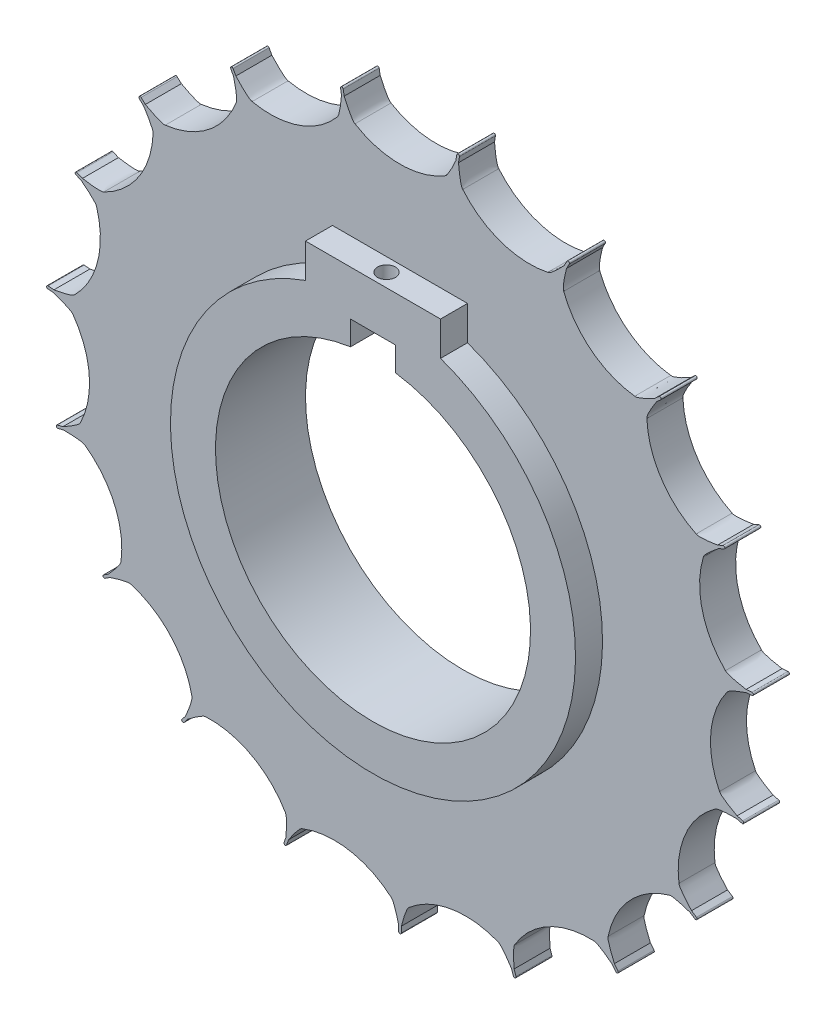
SolidWorks part; units mm, degrees
ref_plane "Front" through (0, 0, 0) normal (0, 0, 1) x (1, 0, 0)
ref_plane "Top" through (0, 0, 0) normal (0, 1, 0) x (1, 0, 0)
ref_plane "Right" through (0, 0, 0) normal (1, 0, 0) x (0, 0, -1)
sketch "Sketch1" plane through (0, 0, 0) normal (0, 0, 1) x (1, 0, 0)
  circle A0 centre (0, 0) radius 36.375
  dimension "D1" = 72.75
extrude "Boss-Extrude1" add sketch "Sketch1" along normal blind 2 and the other way blind 2
sketch "Sketch2" plane through (0, 0, 2) normal (0, 0, 1) x (1, 0, 0)
  line L0 (0, 34.625) -> (0, 34.6205) construction
  line L1 (0, 34.6205) -> (0, 34.625) construction
  line L2 (0, 36.375) -> (0, 34.625) construction
  line L6 (0, 34.6205) -> (0, 34.625)
  arc A0 (-5, 36.0297) -> (5, 36.0297) centre (0, 44.3265) ccw
  arc A1 (7.1254, 39.2332) -> (-7.1254, 39.2332) centre (0, 0) ccw
  circle A2 centre (0, 0) radius 36.375 construction
  spline S0 degree 3 poles (-5, 36.0297) (-5.1674, 36.1306) (-5.4326, 36.5395) (-5.8556, 37.287) (-6.2657, 38.3105) (-6.7543, 39.0109) (-7.1254, 39.2332) knots 0 0 0 0 0.148725 0.362283 0.669737 1 1 1 1
  spline S1 degree 3 poles (5, 36.0297) (5.1674, 36.1306) (5.4326, 36.5395) (5.8556, 37.287) (6.2657, 38.3105) (6.7543, 39.0109) (7.1254, 39.2332) knots 0 0 0 0 0.148725 0.362283 0.669737 1 1 1 1
  circle M4 centre (0, 0) radius 36.375
  dimension "D4" = 79.75
  dimension "D1" = 1.75
extrude "Boss-Extrude2" add sketch "Sketch2" against normal blind 9 contours S1 A1 S0 M4 | A0 M4 region at (0, 35.6073, 2) region at (0, 38.0523, 2)
sketch "Sketch3" plane through (0, 0, 2) normal (0, 0, 1) x (1, 0, 0)
  circle A0 centre (0, 0) radius 39.875
  dimension "D1" = 79.75
extrude "Boss-Extrude3" add sketch "Sketch3" against normal up to surface (4 mm away) up to face at (0, -0.8677, -2)
sketch "Sketch5" plane through (0, 0, 2) normal (0, 0, 1) x (1, 0, 0)
  line L2 (-2.5, 20) -> (2.5, 20)
  line L3 (-2.5, 20) -> (-2.5, 17.3205)
  line L5 (2.5, 20) -> (2.5, 17.3205)
  arc A0 (-2.5, 17.3205) -> (2.5, 17.3205) centre (0, 0) ccw
  dimension "D1" = 35
  dimension "D2" = 5
extrude "Cut-Extrude2" cut sketch "Sketch5" against normal blind 9
sketch "Sketch6" plane through (0, 0, 2) normal (0, 0, 1) x (1, 0, 0)
  line L1 (2.5, 20) -> (-2.5, 20) construction
  line L2 (2.5, 17.3205) -> (2.5, 20) construction
  line L3 (2.5, 17.3205) -> (2.5, 20)
  line L4 (2.5, 20) -> (-2.5, 20)
  line L5 (-2.5, 20) -> (-2.5, 17.3205) construction
  line L6 (-2.5, 20) -> (-2.5, 17.3205)
  line L7 (7.5, 21.2132) -> (7.5, 25)
  line L8 (7.5, 25) -> (-7.5, 25)
  line L9 (-7.5, 25) -> (-7.5, 21.2132)
  arc A0 (-2.5, 17.3205) -> (2.5, 17.3205) centre (0, 0) ccw construction
  arc A1 (-2.5, 17.3205) -> (2.5, 17.3205) centre (0, 0) ccw
  arc A2 (-7.5, 21.2132) -> (7.5, 21.2132) centre (0, 0) ccw
  dimension "D1" = 5
extrude "Boss-Extrude5" add sketch "Sketch6" along normal blind 3 and the other way blind 7
sketch "Sketch7" plane through (0, 25, 0) normal (0, 1, 0) x (1, 0, 0)
  circle A0 centre (0, -3.5) radius 1
  dimension "D1" = 2
extrude "Cut-Extrude3" cut sketch "Sketch7" against normal blind 10
sketch "Sketch11" plane through (0, 0, -7) normal (0, 0, -1) x (-1, 0, 0)
  arc A2 (7.1254, 39.2332) -> (-7.1254, 39.2332) centre (0, 0) ccw
  arc A3 (-5, 36.0297) -> (5, 36.0297) centre (0, 44.3265) ccw
  arc A4 (7.1254, 39.2332) -> (-7.1254, 39.2332) centre (0, 0) ccw
  arc A5 (-5, 36.0297) -> (5, 36.0297) centre (0, 44.3265) ccw
  spline S2 degree 3 poles (-1855.7933, 2388.9541) (-7.8986, 24.7055) (2.4542, 31.2769) (5.8556, 37.287) (10.4797, 48.8278) (54.2774, 45.7402) (1577.4288, -2516.5266) knots -4.715154 -4.715154 -4.715154 -4.715154 0.148725 0.362283 0.669737 9.747756 9.747756 9.747756 9.747756 only from (5, 36.0297) to (7.1254, 39.2332)
  spline S3 degree 3 poles (-1577.4215, -2516.5144) (-54.2772, 45.7402) (-10.4797, 48.8278) (-5.8556, 37.287) (-2.4542, 31.2769) (7.8988, 24.7053) (1855.8507, 2389.0275) knots -8.747742 -8.747742 -8.747742 -8.747742 0.330263 0.637717 0.851275 5.715204 5.715204 5.715204 5.715204 only from (-7.1254, 39.2332) to (-5, 36.0297)
  spline S4 degree 3 poles (5, 36.0297) (5.1674, 36.1306) (5.4326, 36.5395) (5.8556, 37.287) (6.2657, 38.3105) (6.7543, 39.0109) (7.1254, 39.2332) knots 0 0 0 0 0.148725 0.362283 0.669737 1 1 1 1
  spline S5 degree 3 poles (-7.1254, 39.2332) (-6.7543, 39.0109) (-6.2657, 38.3105) (-5.8556, 37.287) (-5.4326, 36.5395) (-5.1674, 36.1306) (-5, 36.0297) knots 0 0 0 0 0.330263 0.637717 0.851275 1 1 1 1
  dimension "D1" = 0
extrude "Cut-Extrude4" cut sketch "Sketch11" against normal up to next
pattern_circular "CirPattern1" count 19 over 360 about axis through (0, 0, 2) along (0, 0, 1) of "Cut-Extrude4"
sketch "Sketch12" plane through (0, 0, 2) normal (0, 0, 1) x (1, 0, 0)
  line L0 (-6.9697, 35.701) -> (-5, 36.0297) construction
  line L1 (-6.4224, 38.4871) -> (-5.9849, 35.8654) construction
  line L2 (-6.4993, 38.0369) -> (-6.2034, 38.0863)
  line L3 (-6.2034, 38.0863) -> (-6.3351, 38.8754)
  line L4 (-6.3351, 38.8754) -> (-6.631, 38.826)
  line L5 (-6.631, 38.826) -> (-6.4993, 38.0369)
  spline S0 degree 3 poles (-6.4224, 38.4871) (-6.4407, 38.4048) (-6.5305, 37.9252) (-6.5687, 37.168) (-6.7261, 36.3237) (-6.8442, 35.8508) (-6.9697, 35.701) knots 0.265932 0.265932 0.265932 0.265932 0.330263 0.637717 0.851275 1 1 1 1 construction
  spline S1 degree 3 poles (-6.4224, 38.4871) (-6.3783, 38.4152) (-6.1376, 37.9908) (-5.8556, 37.287) (-5.4326, 36.5395) (-5.1674, 36.1306) (-5, 36.0297) knots 0 0 0 0 0.064331 0.371786 0.585343 0.734068 0.734068 0.734068 0.734068 construction
  dimension "D1" = 0.3
  dimension "D2" = 0.8
extrude "Boss-Extrude6" add sketch "Sketch12" against normal up to surface (4 mm away) up to face at (0, 12.1783, -2)
fillet "Fillet1" 2 edges at (-6.631, 38.826, 0) (-6.3351, 38.8754, 0) type full round first side face at (-6.5652, 38.4315, 0) second side face at (-6.2692, 38.4809, 0) middle face at (-6.483, 38.8507, 0)
pattern_circular "CirPattern2" count 19 over 360 about axis through (0, 0, 5) along (0, 0, 1) of "Boss-Extrude6", "Fillet1"
